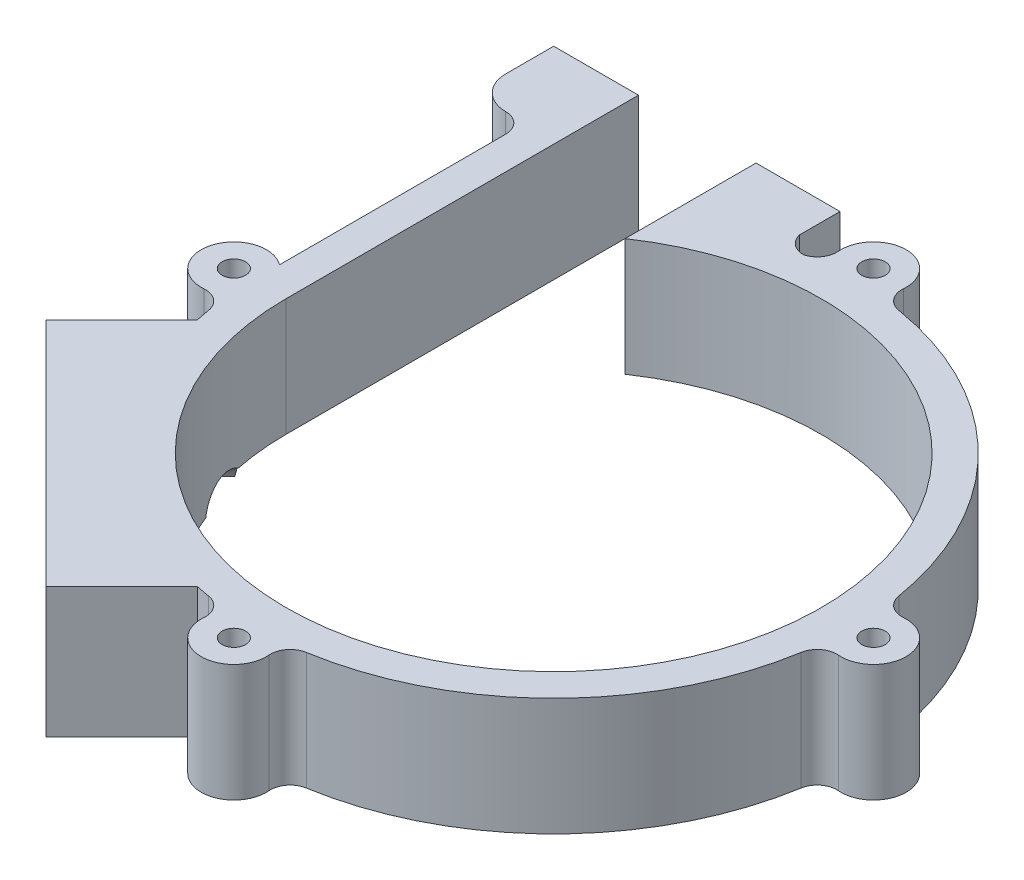
SolidWorks part; units mm, degrees
material "6061 合金"
ref_plane "前视基准面" through (0, 0, 0) normal (0, 0, 1) x (1, 0, 0)
ref_plane "上视基准面" through (0, 0, 0) normal (0, 1, 0) x (1, 0, 0)
ref_plane "右视基准面" through (0, 0, 0) normal (1, 0, 0) x (0, 0, -1)
sketch "草图1" plane through (0, 0, 0) normal (0, 1, 0) x (1, 0, 0)
  line L0 (-32, 0) -> (-32, 54) construction
  line L1 (-41, 0) -> (-41, 54)
  line L2 (-23, 54) -> (-23, 33.9411)
  line L3 (-41, 54) -> (-46, 54)
  line L4 (-46, 54) -> (-46, 50.6476)
  line L5 (-49, 0) -> (-49, 54) construction
  line L6 (-23, 54) -> (-18, 54)
  line L8 (-18, 54) -> (-18, 50.6476)
  line L10 (-49, 46.6476) -> (-15, 46.6476) construction
  line L11 (-46, 42.6476) -> (-46, 4)
  arc A0 (-41, 0) -> (-23, 33.9411) centre (0, 0) ccw
  circle A1 centre (0, 0) radius 49 construction
  circle A2 centre (0, 0) radius 32 construction
  circle A4 centre (0, 0) radius 41 construction
  circle A5 centre (0, 49) radius 1.8
  circle A6 centre (49, 0) radius 1.8
  circle A7 centre (0, -49) radius 1.8
  circle A8 centre (-49, 0) radius 1.8
  arc A35 (3.8722, 45.8367) -> (-3.8722, 45.8367) centre (0, 49) ccw
  arc A36 (-45.8367, -3.8722) -> (-3.8722, -45.8367) centre (0, 0) ccw
  arc A37 (45.8367, -3.8722) -> (45.8367, 3.8722) centre (49, 0) ccw
  arc A38 (-3.8722, -45.8367) -> (3.8722, -45.8367) centre (0, -49) ccw
  arc A39 (-46, 4) -> (-45.8367, -3.8722) centre (-49, 0) ccw
  arc A40 (-3.8722, 45.8367) -> (-10.3454, 44.8216) centre (0, 0) ccw
  arc A41 (45.8367, 3.8722) -> (3.8722, 45.8367) centre (0, 0) ccw
  arc A42 (3.8722, -45.8367) -> (45.8367, -3.8722) centre (0, 0) ccw
  circle A45 centre (-15, 46.6476) radius 1.8
  circle A47 centre (-49, 46.6476) radius 1.8
  arc A48 (-46, 50.6476) -> (-46, 42.6476) centre (-49, 46.6476) ccw
  arc A50 (-10.3454, 44.8216) -> (-18, 50.6476) centre (-15, 46.6476) ccw
  dimension "D1" = 82
  dimension "D3" = 9
  dimension "D6" = 3.6
  dimension "D8" = 8
  dimension "D12" = 8
  dimension "D4" = 54
  dimension "D9" = 10
  dimension "D2" = 5
  dimension "D5" = 9
  dimension "D10" = 5
  dimension "D11" = 5
  dimension "D7" = 4
extrude "凸台-拉伸1" add sketch "草图1" along normal blind 18
fillet "圆角1" radius 3 11 edges at (-3.8722, 9, -45.8367) (3.8722, 9, -45.8367) (45.8367, 9, -3.8722) (45.8367, 9, 3.8722) (3.8722, 9, 45.8367) (-3.8722, 9, 45.8367) (-45.8367, 9, 3.8722) (-46, 9, -42.6476) (-46, 9, -50.6476) (-18, 9, -50.6476) (-10.3454, 9, -44.8216)
sketch "草图2" plane through (0, 0, 0) normal (0, -1, 0) x (1, 0, 0)
  line L0 (0, 0) -> (-32.5269, 32.5269) construction
  line L1 (0, 0) -> (-41, 0) construction
  line L2 (-44.9815, 9.6262) -> (-40.6559, 5.3006)
  line L3 (-9.6262, 44.9815) -> (-5.3006, 40.6559)
  arc A0 (-7.4851, 45.3869) -> (-45.3869, 7.4851) centre (0, 0) ccw construction
  arc A1 (-23, -33.9411) -> (-41, 0) centre (0, 0) ccw construction
  arc A2 (-44.9815, 9.6262) -> (-9.6262, 44.9815) centre (0, 0) cw
  arc A3 (-40.6559, 5.3006) -> (-5.3006, 40.6559) centre (0, 0) cw
  dimension "D1" = 45
  dimension "D2" = 50
extrude "凸台-拉伸2" add sketch "草图2" along normal blind 2
fillet "圆角3" radius 2 2 edges at (-40.6559, -1, 5.3006) (-5.3006, -1, 40.6559)
ref_plane "基准面1" through (0, -3, 0) normal (0, -1, 0) x (-1, 0, 0)
sketch "草图3" plane through (0, -3, 0) normal (0, -1, 0) x (-1, 0, 0)
  line L0 (39.598, -39.598) -> (25.4558, -25.4558) construction
  line L1 (28.2843, -49.4975) -> (21.2132, -42.4264)
  line L2 (21.2132, -36.7696) -> (28.9914, -28.9914) construction
  line L3 (28.9914, -28.9914) -> (38.8909, -38.8909)
  line L4 (38.8909, -38.8909) -> (28.2843, -49.4975) construction
  line L5 (21.2132, -42.4264) -> (21.2132, -37.1838)
  line L6 (25.4558, -25.4558) -> (28.9914, -28.9914)
  line L7 (0, 0) -> (25.4558, -25.4558) construction
  line L8 (0, 0) -> (41, 0) construction
  line L12 (21.2132, -36.7696) -> (23.776, -34.2067)
  line L13 (39.598, -39.598) -> (28.9914, -50.2046)
  line L14 (28.9914, -50.2046) -> (28.2843, -49.4975)
  line L15 (38.8909, -38.8909) -> (39.598, -39.598)
  line L16 (19.0919, -34.6482) -> (23.1445, -30.5956)
  line L17 (19.0919, -34.6482) -> (20.9203, -36.4767)
  arc A0 (25.4558, -25.4558) -> (23.776, -34.2067) centre (31.0703, -31.0703) ccw
  arc A4 (21.2132, -37.1838) -> (20.9203, -36.4767) centre (20.2132, -37.1838) ccw
  dimension "D5" = 10
  dimension "D11" = 7.94
  dimension "D6" = 1
  dimension "D2" = 20
  dimension "D3" = 15
  dimension "D4" = 11
  dimension "D7" = 5
  dimension "D8" = 1
  dimension "D9" = 45
  dimension "D10" = 36
  dimension "D13" = 3
ref_plane "基准面2" through (-32.5269, 0, 32.5269) normal (-0.7071, 0, 0.7071) x (0.7071, 0, 0.7071)
sketch "草图4" plane through (-32.5269, 0, 32.5269) normal (-0.7071, 0, 0.7071) x (0.7071, 0, 0.7071)
  line L0 (0, -3) -> (0, 14.5) construction
  line L1 (-25, -3) -> (25, -3) construction
  line L2 (-23.125, -6.9031) -> (-10.9375, -16.6609)
  line L3 (-23.125, 0.9031) -> (-10.9375, 10.6609)
  line L4 (0, -3) -> (0, -20.5) construction
  line L5 (23.125, 0.9031) -> (10.9375, 10.6609)
  line L6 (23.125, -6.9031) -> (10.9375, -16.6609)
  line L7 (-25, -2) -> (25, -2) construction
  line L9 (-24.899, -2) -> (24.899, -2)
  arc A0 (-10.9375, -16.6609) -> (10.9375, -16.6609) centre (0, -3) ccw
  circle A1 centre (-20, -3) radius 2
  arc A2 (-23.125, 0.9031) -> (-23.125, -6.9031) centre (-20, -3) ccw
  circle A3 centre (20, -3) radius 2
  arc A4 (10.9375, 10.6609) -> (-10.9375, 10.6609) centre (0, -3) ccw
  arc A5 (23.125, 0.9031) -> (23.125, -6.9031) centre (20, -3) cw
  point P12 (0, -3)
  dimension "D4" = 4
  dimension "D1" = 40
  dimension "D2" = 35
  dimension "D3" = 50
  dimension "D5" = 1
extrude "凸台-拉伸3" add sketch "草图4" along normal blind 9 and the other way up to surface contours A5 L5 A4 L3 A2 L9 A1 A3 | A3 L9 | L9 A1
sketch "草图5" plane through (-38.8909, 0, 38.8909) normal (-0.7071, 0, 0.7071) x (0.7071, 0, 0.7071)
  line L0 (-20, -3) -> (20, -3) construction
  line L1 (0, -3) -> (0, -2) construction
  line L2 (-24.899, -2) -> (24.899, -2) construction
  circle A0 centre (-20, -3) radius 4
  circle A1 centre (20, -3) radius 4
  dimension "D3" = 8
  dimension "D1" = 1
  dimension "D2" = 40
extrude "切除-拉伸1" cut sketch "草图5" against normal up to surface (17.2508 mm away)
revolve "切除-旋转5" cut sketch "草图3" angle 360 about L3
fillet "圆角6" radius 0.5 2 edges at (-21.0197, 1.5204, 35.2018) (-34.4226, 3.8697, 22.2729)
sketch "草图7" plane through (-46, 0, 0) normal (-1, 0, 0) x (0, 0, 1)
  line L0 (0, 0) -> (0, 9)
  line L1 (-82.32, -10.32) -> (-64.32, -10.32)
  line L2 (0, 9) -> (-54, 9) construction
  line L4 (-54, 18) -> (-54, 0) construction
  arc A0 (-54, 9) -> (-73.32, -10.32) centre (-54, -10.32) ccw construction
  arc A1 (-54, 18) -> (-82.32, -10.32) centre (-54, -10.32) ccw
  arc A2 (-54, 0) -> (-64.32, -10.32) centre (-54, -10.32) ccw
  dimension "D1" = 19.32
fillet "圆角7" radius 3 1 edges at (-38.8909, 12, 38.8909)
sketch "草图8" plane through (-38.8909, 0, 38.8909) normal (-0.7071, 0, 0.7071) x (0.7071, 0, 0.7071)
  line L0 (-24.899, -2) -> (-25, -2)
  line L1 (-25, -2) -> (-25, 18)
  line L2 (26.8006, 18) -> (-26.8006, 18) construction
  line L3 (-25, 18) -> (25, 18)
  line L4 (25, 18) -> (25, -2)
  line L5 (25, -2) -> (24.899, -2)
  line L6 (23.125, 0.9031) -> (14.2263, 8.0278) construction
  line L7 (14.2263, 8.0278) -> (10.9375, 10.6609) construction
  line L8 (-10.9375, 10.6609) -> (-14.2263, 8.0278) construction
  line L9 (-23.125, 0.9031) -> (-14.2263, 8.0278) construction
  line L10 (23.125, 0.9031) -> (14.2263, 8.0278)
  line L11 (14.2263, 8.0278) -> (10.9375, 10.6609)
  line L12 (-10.9375, 10.6609) -> (-14.2263, 8.0278)
  line L13 (-23.125, 0.9031) -> (-14.2263, 8.0278)
  arc A0 (-23.125, 0.9031) -> (-24.899, -2) centre (-20, -3) ccw construction
  arc A1 (-23.125, 0.9031) -> (-24.899, -2) centre (-20, -3) ccw
  arc A2 (24.899, -2) -> (23.125, 0.9031) centre (20, -3) ccw construction
  arc A3 (10.9375, 10.6609) -> (-10.9375, 10.6609) centre (0, -3) ccw construction
  arc A4 (24.899, -2) -> (23.125, 0.9031) centre (20, -3) ccw
  arc A5 (10.9375, 10.6609) -> (-10.9375, 10.6609) centre (0, -3) ccw
extrude "凸台-拉伸4" add sketch "草图8" against normal up to surface (15.2353 mm away)
sketch "草图9" plane through (0, 0, 0) normal (0, -1, 0) x (1, 0, 0)
  line L0 (-54, -46.6697) -> (-54, -54)
  line L1 (-54, -54) -> (-46, -54)
  line L4 (-18, -54) -> (-10.131, -54)
  line L5 (-10.131, -54) -> (-10.131, -47.7846)
  arc A0 (-49, -41.6476) -> (-48.9558, -51.6474) centre (-49, -46.6476) ccw construction
  arc A1 (-46, -54) -> (-48.9558, -51.6474) centre (-48.9293, -54.6473) ccw construction
  arc A2 (-46, -54) -> (-48.9558, -51.6474) centre (-48.9293, -54.6473) ccw
  arc A3 (-54, -46.6697) -> (-48.9558, -51.6474) centre (-49, -46.6476) ccw
  arc A4 (-15.0442, -51.6474) -> (-10.131, -47.7846) centre (-15, -46.6476) ccw construction
  arc A5 (-15.0442, -51.6474) -> (-18, -54) centre (-15.0707, -54.6473) ccw construction
  arc A6 (-15.0442, -51.6474) -> (-10.131, -47.7846) centre (-15, -46.6476) ccw
  arc A7 (-15.0442, -51.6474) -> (-18, -54) centre (-15.0707, -54.6473) ccw
  circle A8 centre (-15, -46.6476) radius 1.8 construction
  circle A9 centre (-49, -46.6476) radius 1.8 construction
  circle A10 centre (-15, -46.6476) radius 1.8
  circle A11 centre (-49, -46.6476) radius 1.8
extrude "凸台-拉伸5" add sketch "草图9" against normal up to surface (18 mm away) up to face at (-15, 18, -44.8476)
sketch "草图10" plane through (0, 0, -54) normal (0, 0, -1) x (-1, 0, 0)
  line L0 (47.5, 4) -> (47.5, 14) construction
  line L2 (41, 18) -> (41, 0) construction
  line L3 (41, 0) -> (54, 0) construction
  line L4 (41, 0) -> (23, 0) construction
  line L5 (32, 0) -> (32, 18) construction
  line L6 (41, 18) -> (54, 18) construction
  circle A0 centre (47.5, 4) radius 2.35
  circle A1 centre (47.5, 14) radius 2.35
  circle A2 centre (16.5, 14) radius 2.35
  circle A3 centre (16.5, 4) radius 2.35
  point P15 (0, 0)
  dimension "D4" = 4.7
  dimension "D1" = 10
  dimension "D2" = 6.5
  dimension "D3" = 4
extrude "热熔螺母安装孔" cut sketch "草图10" against normal blind 7
sketch "草图11" plane through (0, 0, 0) normal (0, -1, 0) x (1, 0, 0)
  circle A0 centre (-15, -46.6476) radius 1.8 construction
  circle A1 centre (-49, -46.6476) radius 1.8 construction
  circle A2 centre (-15, -46.6476) radius 1.8 construction
  circle A3 centre (-49, -46.6476) radius 1.8 construction
  circle A4 centre (-49, -46.6476) radius 2.35
  circle A5 centre (-15, -46.6476) radius 2.35
  dimension "D1" = 4.7
extrude "切除-拉伸3" cut sketch "草图11" against normal blind 10
